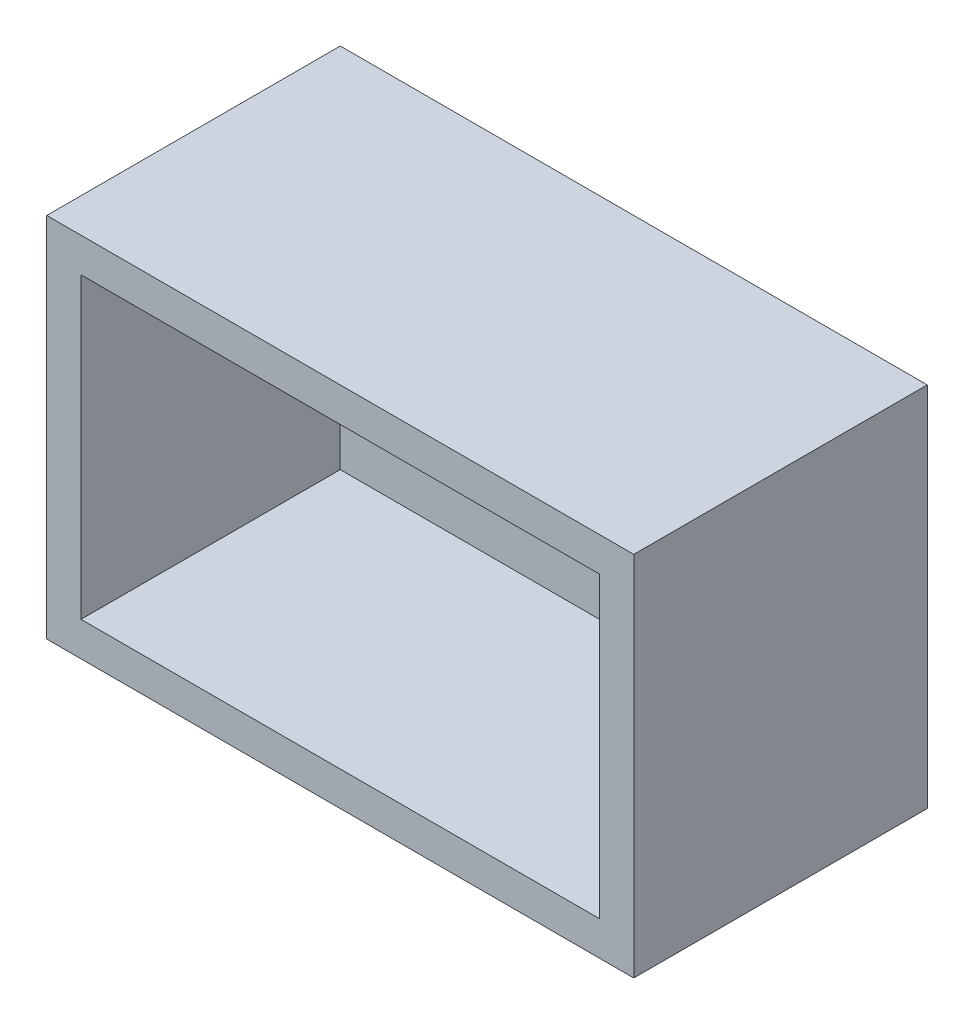
SolidWorks part; units mm, degrees
ref_plane "Přední rovina" through (0, 0, 0) normal (0, 0, 1) x (1, 0, 0)
ref_plane "Horní rovina" through (0, 0, 0) normal (0, 1, 0) x (1, 0, 0)
ref_plane "Pravá rovina" through (0, 0, 0) normal (1, 0, 0) x (0, 0, -1)
sketch "Skica1" plane through (0, 0, 0) normal (0, 0, 1) x (1, 0, 0)
  line L1 (-60, 37.5) -> (60, 37.5)
  line L2 (-60, 37.5) -> (-60, -37.5)
  line L3 (-60, -37.5) -> (60, -37.5)
  line L4 (60, 37.5) -> (60, -37.5)
  line L5 (-60, 37.5) -> (60, -37.5) construction
  line L6 (-60, -37.5) -> (60, 37.5) construction
  point P0 (0, 0)
  dimension "D1" = 120
  dimension "D2" = 75
extrude "Přidat vysunutím9" add sketch "Skica1" along normal blind 7 contours L1 L4 L3 L2
sketch "Skica9" plane through (-60, 0, 0) normal (-1, 0, 0) x (0, 0, 1)
  line L1 (0, -37.5) -> (60, -37.5)
  line L2 (0, -37.5) -> (0, 37.5)
  line L3 (0, 37.5) -> (60, 37.5)
  line L4 (60, -37.5) -> (60, 37.5)
  dimension "D1" = 60
  dimension "D2" = 75
extrude "Přidat vysunutím10" add sketch "Skica9" against normal blind 7
sketch "Skica10" plane through (60, 0, 0) normal (1, 0, 0) x (0, 0, -1)
  line L1 (0, -37.5) -> (-60, -37.5)
  line L2 (0, -37.5) -> (0, 37.5)
  line L3 (0, 37.5) -> (-60, 37.5)
  line L4 (-60, -37.5) -> (-60, 37.5)
extrude "Přidat vysunutím11" add sketch "Skica10" against normal blind 7
sketch "Skica11" plane through (0, -37.5, 0) normal (0, -1, 0) x (-1, 0, 0)
  line L1 (60, 0) -> (-60, 0)
  line L2 (60, 0) -> (60, -60)
  line L3 (60, -60) -> (-60, -60)
  line L4 (-60, 0) -> (-60, -60)
extrude "Přidat vysunutím12" add sketch "Skica11" against normal blind 7
sketch "Skica12" plane through (0, 37.5, 0) normal (0, 1, 0) x (1, 0, 0)
  line L1 (-60, 0) -> (60, 0)
  line L2 (-60, 0) -> (-60, -60)
  line L3 (-60, -60) -> (60, -60)
  line L4 (60, 0) -> (60, -60)
extrude "Přidat vysunutím13" add sketch "Skica12" against normal blind 7
